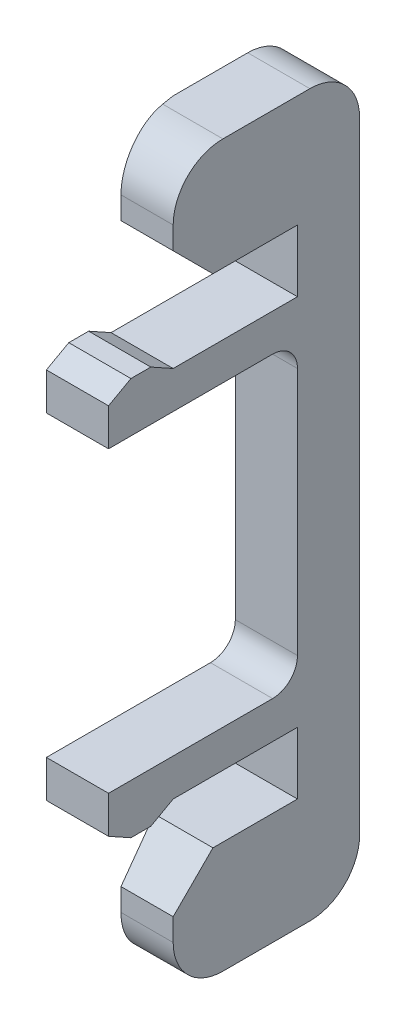
SolidWorks part; units mm, degrees
ref_plane "Front Plane" through (0, 0, 0) normal (0, 0, 1) x (1, 0, 0)
ref_plane "Top Plane" through (0, 0, 0) normal (0, 1, 0) x (1, 0, 0)
ref_plane "Right Plane" through (0, 0, 0) normal (1, 0, 0) x (0, 0, -1)
sketch "Sketch1" plane through (0, 0, 0) normal (0, 0, 1) x (1, 0, 0)
  line L1 (-1.5875, -18.415) -> (1.5875, -18.415)
  line L2 (-1.5875, -18.415) -> (-1.5875, 18.415)
  line L3 (-1.5875, 18.415) -> (1.5875, 18.415)
  line L4 (1.5875, -18.415) -> (1.5875, 18.415)
  line L5 (-1.5875, -18.415) -> (1.5875, 18.415) construction
  line L6 (-1.5875, 18.415) -> (1.5875, -18.415) construction
  point P0 (0, 0)
  dimension "D1" = 36.83
  dimension "D2" = 3.175
extrude "Base" add sketch "Sketch1" along normal blind 3.175
sketch "Sketch3" plane through (-1.5875, 0, 0) normal (-1, 0, 0) x (0, 0, 1)
  line L0 (3.175, 12.7) -> (9.525, 12.7)
  line L1 (3.175, 18.415) -> (3.175, -18.415) construction
  line L3 (3.175, -12.7) -> (9.525, -12.7)
  line L5 (3.175, 18.415) -> (3.175, 12.7)
  line L6 (3.175, -12.7) -> (3.175, -18.415)
  line L7 (3.175, 18.415) -> (9.525, 18.415)
  line L9 (3.175, -18.415) -> (9.525, -18.415)
  line L10 (9.525, -18.415) -> (9.525, -12.7)
  line L11 (9.525, 18.415) -> (9.525, 12.7)
  dimension "D1" = 6.35
  dimension "D2" = 25.4
extrude "Retainer" add sketch "Sketch3" against normal up to surface (3.175 mm away) up to face at (1.5875, 0, 1.5875)
sketch "Sketch5" plane through (-1.5875, 0, 0) normal (-1, 0, 0) x (0, 0, 1)
  line L0 (3.175, 9.525) -> (9.525, 9.525)
  line L1 (3.175, 12.7) -> (3.175, -12.7) construction
  line L2 (9.525, 9.525) -> (10.668, 10.16)
  line L3 (10.668, 10.16) -> (11.684, 10.16)
  line L4 (11.684, 10.16) -> (12.827, 9.525)
  line L5 (12.827, 9.525) -> (12.827, 7.62)
  line L6 (12.827, 7.62) -> (3.175, 7.62)
  line L7 (3.175, 9.525) -> (12.827, 9.525) construction
  line L8 (3.175, 12.7) -> (9.525, 12.7) construction
  line L9 (3.175, 0) -> (18.8887, 0) construction
  line L10 (3.175, -9.525) -> (12.827, -9.525) construction
  line L11 (12.827, -7.62) -> (3.175, -7.62)
  line L12 (12.827, -9.525) -> (12.827, -7.62)
  line L13 (11.684, -10.16) -> (12.827, -9.525)
  line L14 (10.668, -10.16) -> (11.684, -10.16)
  line L15 (9.525, -9.525) -> (10.668, -10.16)
  line L16 (3.175, -9.525) -> (9.525, -9.525)
  line L17 (3.175, 9.525) -> (3.175, 7.62)
  line L18 (3.175, -7.62) -> (3.175, -9.525)
  dimension "D1" = 6.35
  dimension "D2" = 1.905
  dimension "D3" = 1.016
  dimension "D4" = 9.652
  dimension "D5" = 0.635
  dimension "D6" = 3.175
extrude "Tab" add sketch "Sketch5" against normal up to surface (3.175 mm away) up to face at (1.5875, 0, 5.5562)
fillet "Fillet1" radius 1.27 2 edges at (0, -7.62, 3.175) (0, 7.62, 3.175)
fillet "Fillet2" radius 2.54 4 edges at (0, 18.415, 0) (0, -18.415, 0) (0, -18.415, 9.525) (0, 18.415, 9.525)
chamfer "Chamfer1" distance 2.032 angle 45 2 edges at (0, -12.7, 9.525) (0, 12.7, 9.525)
sketch "Sketch6" plane through (0, 18.415, 0) normal (0, 1, 0) x (1, 0, 0)
  line L0 (-1.5875, -6.35) -> (-1.0795, -9.525)
  line L1 (-1.5875, -6.985) -> (-1.5875, -2.54) construction
  line L2 (-1.0795, -9.525) -> (-1.5875, -9.525)
  line L3 (-1.5875, -9.525) -> (-1.5875, -6.35)
  line L4 (-1.5875, -9.525) -> (1.5875, -9.525) construction
  dimension "D1" = 3.175
  dimension "D2" = 0.508
extrude "Cut-Extrude1" cut sketch "Sketch6" against normal up to next
mirror "Mirror1" about plane through (0, 0, 0) normal (0, 1, 0) of "Cut-Extrude1"
